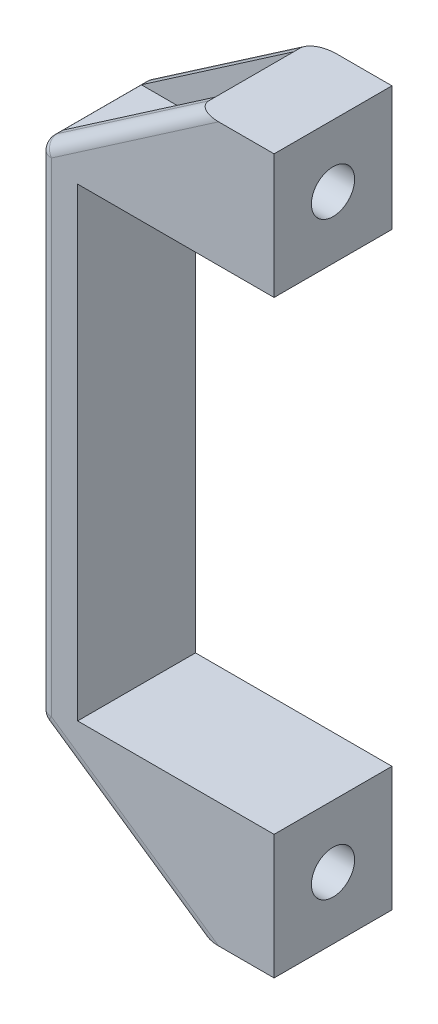
SolidWorks part; units mm, degrees
ref_plane "前视基准面" through (0, 0, 0) normal (0, 0, 1) x (1, 0, 0)
ref_plane "上视基准面" through (0, 0, 0) normal (0, 1, 0) x (1, 0, 0)
ref_plane "右视基准面" through (0, 0, 0) normal (1, 0, 0) x (0, 0, -1)
sketch "草图1" plane through (0, 0, 0) normal (0, 0, 1) x (1, 0, 0)
  line L0 (0, 0) -> (-12, 0)
  line L1 (-12, 0) -> (-36, 16.5)
  line L2 (-36, 16.5) -> (-36, 92.5)
  line L3 (-36, 92.5) -> (-12, 109)
  line L4 (-12, 109) -> (0, 109)
  line L5 (0, 109) -> (0, 90)
  line L6 (0, 90) -> (-30, 90)
  line L7 (-30, 90) -> (-30, 19)
  line L8 (-30, 19) -> (0, 19)
  line L9 (0, 19) -> (0, 0)
  line L10 (-36, 54.5) -> (24.6077, 54.5) construction
  point P13 (-30, 54.5)
  dimension "D1" = 6
  dimension "D2" = 36
  dimension "D3" = 109
  dimension "D4" = 12
  dimension "D5" = 19
  dimension "D6" = 76
extrude "凸台-拉伸1" add sketch "草图1" along normal mid plane 18
sketch "草图2" plane through (-36, 0, 0) normal (-1, 0, 0) x (0, 0, 1)
  line L1 (-6, 93) -> (6, 93)
  line L2 (-6, 93) -> (-6, 109)
  line L3 (-6, 109) -> (6, 109)
  line L4 (6, 93) -> (6, 109)
  line L7 (9, 109) -> (9, 92.5) construction
  line L8 (-9, 109) -> (-9, 92.5) construction
  line L9 (9, 109) -> (-9, 109) construction
  dimension "D1" = 3
  dimension "D2" = 3
  dimension "D3" = 16
extrude "切除-拉伸1" cut sketch "草图2" against normal blind 24
ref_plane "基准面1" through (0, 54.5, 0) normal (0, 1, 0) x (-1, 0, 0)
hole_wizard "打孔尺寸根据内六角花形圆柱头螺钉-4.8级的类型1" positions "草图4" profile "草图3" counterbore size "M6" standard "GB" end condition through all
sketch "草图4" plane through (-12, 0, 0) normal (-1, 0, 0) x (0, 0, 1)
  line L0 (9, 92.5) -> (9, 16.5) construction
  point P0 (0, 99.5)
  point P3 (9, 54.5)
  dimension "D1" = 45
sketch "草图3" plane through (-12, 99.5, 0) normal (0, 1, 0) x (0, 0, 1)
  line L0 (0, 0) -> (0, 12)
  line L1 (0, 12) -> (3.3, 12)
  line L3 (3.3, 12) -> (3.3, 4.7)
  line L4 (3.3, 4.7) -> (5.5, 4.7)
  line L5 (5.5, 4.7) -> (5.5, 0)
  line L7 (5.5, 0) -> (0, 0)
  line L11 (0, -6.35) -> (0, 107.95) construction
  dimension "通孔孔直径" = 6.6
  dimension "通孔孔深度" = 12
  dimension "柱形沉头孔直径" = 11
  dimension "柱形沉头孔深度" = 4.7
mirror "镜向1" about plane through (0, 54.5, 0) normal (0, 1, 0) of "打孔尺寸根据内六角花形圆柱头螺钉-4.8级的类型1", "切除-拉伸1"
fillet "圆角1" radius 2 8 edges at (-24, 100.75, -9) (-24, 100.75, 9) (-36, 92.5, 0) (-36, 16.5, 0) (-24, 8.25, 9) (-24, 8.25, -9) (-36, 54.5, -9) (-36, 54.5, 9)
